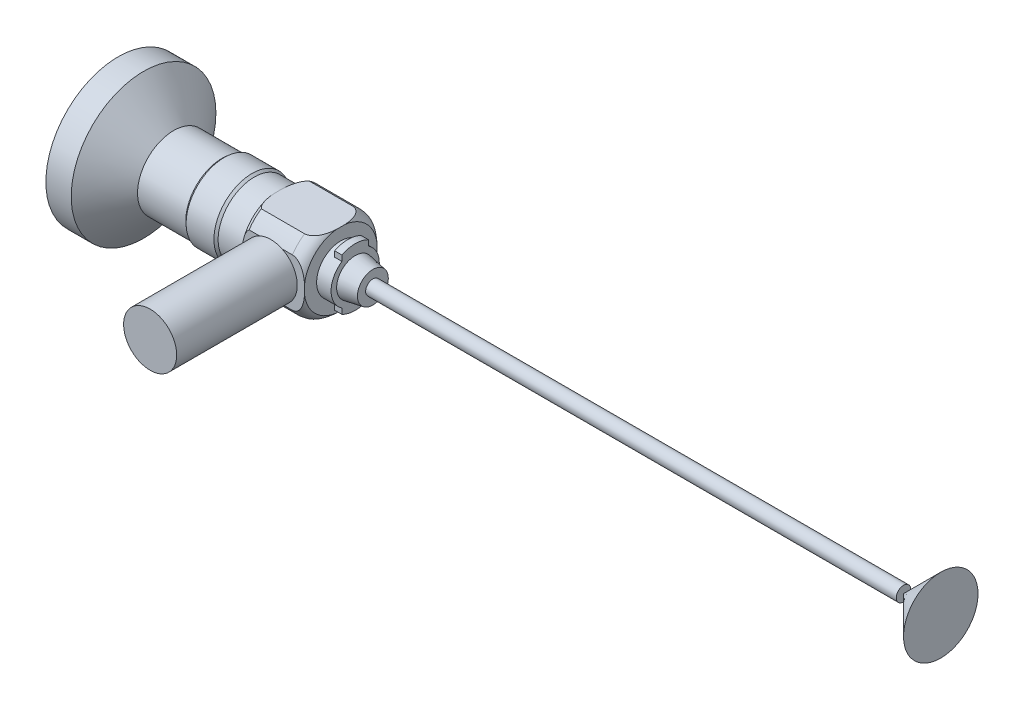
SolidWorks part; units mm, degrees
ref_plane "Front Plane" through (0, 0, 0) normal (0, 0, 1) x (1, 0, 0)
ref_plane "Top Plane" through (0, 0, 0) normal (0, 1, 0) x (1, 0, 0)
ref_plane "Right Plane" through (0, 0, 0) normal (1, 0, 0) x (0, 0, -1)
ref_axis "Axis1" through (88.99, 0, 0) along (-1, 0, 0)
sketch "Sketch1" plane through (0, 0, 0) normal (0, 0, 1) x (1, 0, 0)
  line L0 (-74.5697, 0) -> (-77.8697, -15) construction
  line L1 (-77.8697, -15) -> (-72.6197, -15)
  line L2 (-72.6197, -15) -> (-66.3697, -7.5)
  line L3 (-66.3697, -7.5) -> (-56.3697, -7.5)
  line L4 (-56.3697, -7.5) -> (-55.8897, -7.9)
  line L5 (-55.8897, -7.9) -> (-50.1397, -7.9)
  line L6 (-50.1397, -7.9) -> (-49.6597, -7.5)
  line L7 (-49.6597, -7.5) -> (-44.6597, -7.5)
  line L8 (88.99, 0) -> (-88.99, 0) construction
  line L9 (-74.5697, 0) -> (-25.0835, 0)
  line L10 (-43.2452, -9) -> (-34.2597, -9)
  line L11 (-31.7461, -7.5592) -> (-31.7461, -5)
  line L12 (-31.7461, -5) -> (-30.2461, -5)
  line L13 (-30.2461, -5) -> (-30.2461, -6)
  line L14 (-30.2461, -6) -> (-28.7461, -6)
  line L15 (-28.7461, -6) -> (-28.7461, -3.85)
  line L16 (-28.7461, -3.85) -> (-25.0835, -3.2)
  line L17 (-25.0835, -3.2) -> (-25.0835, 0)
  arc A0 (-74.5697, 0) -> (-77.8697, -15) centre (-129.3209, 4.1823) cw
  arc A1 (-44.6597, -7.5) -> (-40.5597, -9) centre (-41.9025, -6.3168) ccw
  arc A2 (-34.2597, -9) -> (-31.7461, -7.5592) centre (-34.3096, -6) ccw
  point P12 (-40.5597, -9)
  point P16 (-34.2597, -9)
  point P17 (-44.6597, -9)
  point P18 (-37.4097, -9)
  point P20 (-30.1597, -9)
  dimension "D4" = 11.5
  dimension "D12" = 9
  dimension "D13" = 3.15
  dimension "D15" = 5
  dimension "D1" = 5.25
  dimension "D2" = 15
  dimension "D3" = 3.3
  dimension "D5" = 7.5
  dimension "D6" = 5.75
  dimension "D7" = 7.9
  dimension "D8" = 7.5
  dimension "D9" = 10
  dimension "D10" = 5
  dimension "D11" = 14.5
  dimension "D14" = 3.15
  dimension "D16" = 6
  dimension "D17" = 1.5
  dimension "D18" = 1.5
  dimension "D19" = 3.85
  dimension "D20" = 3.2
revolve "Revolve1" add sketch "Sketch1" angle 360 about axis through (88.99, 0, 0) along (-1, 0, 0) region at (-53.5304, -4.7691, 0)
sketch "Sketch2" plane through (-31.7461, 0, 0) normal (1, 0, 0) x (0, 0, -1)
  line L0 (0, 9) -> (0, -9)
  line L1 (12.4327, -7.5) -> (-12.4327, -7.5)
  line L2 (12.4327, -7.5) -> (12.4327, 7.5) construction
  line L3 (12.4327, 7.5) -> (-12.4327, 7.5)
  line L4 (-12.4327, -7.5) -> (-12.4327, 7.5) construction
  line L5 (12.4327, 7.5) -> (-12.4327, -7.5) construction
  line L6 (12.4327, 7.5) -> (12.4327, 11.5013)
  line L7 (12.4327, 11.5013) -> (-12.4327, 11.5013)
  line L8 (-12.4327, 11.5013) -> (-12.4327, 7.5)
  line L9 (-12.4327, -7.5) -> (-12.4327, -12.9232)
  line L10 (-12.4327, -12.9232) -> (12.4327, -12.9232)
  line L11 (12.4327, -12.9232) -> (12.4327, -7.5)
  circle A0 centre (0, 0) radius 9 construction
  circle A1 centre (0, 0) radius 9
  dimension "D1" = 15
extrude "Cut-Extrude1" cut sketch "Sketch2" against normal blind 15 contours L9 L10 L11 L1 | L8 L3 L6 L7
pattern_circular "CirPattern1" count 2 every 90 about axis through (88.99, 0, 0) along (-1, 0, 0) of "Cut-Extrude1"
sketch "Sketch3" plane through (-28.7461, 0, 0) normal (1, 0, 0) x (0, 0, -1)
  line L0 (2.75, 6.4372) -> (2.75, -6.4372) construction
  line L1 (-2.75, -6.4372) -> (-2.75, 6.4372) construction
  line L2 (2.75, -6.4372) -> (-2.75, 6.4372) construction
  line L3 (2.75, -4.1758) -> (2.75, -6.4372)
  line L4 (2.75, -6.4372) -> (-2.75, -6.4372) construction
  line L5 (-2.75, -6.4372) -> (-2.75, -4.1758)
  line L6 (2.75, 4.1758) -> (2.75, 6.4372)
  line L7 (2.75, 6.4372) -> (-2.75, 6.4372) construction
  line L8 (-2.75, 6.4372) -> (-2.75, 4.1758)
  line L9 (2.75, 6.4372) -> (6.4302, 6.4372)
  line L10 (6.4302, 6.4372) -> (5.9638, -6.4372)
  line L11 (5.9638, -6.4372) -> (2.75, -6.4372)
  line L12 (-2.75, -6.4372) -> (-6.2806, -6.4372)
  line L13 (-6.2806, -6.4372) -> (-6.2806, 6.4372)
  line L14 (-6.2806, 6.4372) -> (-2.75, 6.4372)
  circle A0 centre (0, 0) radius 6 construction
  circle A1 centre (0, 0) radius 6 construction
  arc A2 (2.75, -4.1758) -> (2.75, 4.1758) centre (0, 0) ccw
  arc A3 (-2.75, 4.1758) -> (-2.75, -4.1758) centre (0, 0) ccw
  point P3 (7, 0)
  point P4 (0, 0)
  dimension "D1" = 10
  dimension "D3" = 5.5
extrude "Cut-Extrude2" cut sketch "Sketch3" against normal up to surface (1.5 mm away) up to face at (-30.2461, 0, -6)
sketch "Sketch4" plane through (0, 0, 7.5) normal (0, 0, 1) x (1, 0, 0)
  line L0 (-34.2597, 4.9749) -> (-43.2452, -4.9749) construction
  circle A0 centre (-38.7525, 0) radius 5.5
  dimension "D1" = 11
extrude "Boss-Extrude1" add sketch "Sketch4" along normal blind 25
sketch "Sketch5" plane through (-25.0835, 0, 0) normal (1, 0, 0) x (0, 0, -1)
  circle A0 centre (0, 0) radius 1.5
  dimension "D1" = 3
extrude "Boss-Extrude2" add sketch "Sketch5" along normal blind 110
sketch "Sketch6" plane through (0, 0, 0) normal (0, 0, 1) x (1, 0, 0)
  line L0 (84.9165, 0) -> (85.1501, 0)
  line L1 (84.9165, 0) -> (92.6353, 0)
  line L2 (84.9165, -1.5) -> (84.9165, 1.5) construction
  line L3 (84.9165, -1.5) -> (84.9165, 1.5)
  line L4 (84.9165, 0) -> (92.6353, -7.7188)
  line L5 (92.6353, -7.7188) -> (92.6353, 0)
  dimension "D2" = 45
revolve "Revolve2" add sketch "Sketch6" angle 360 about L1
